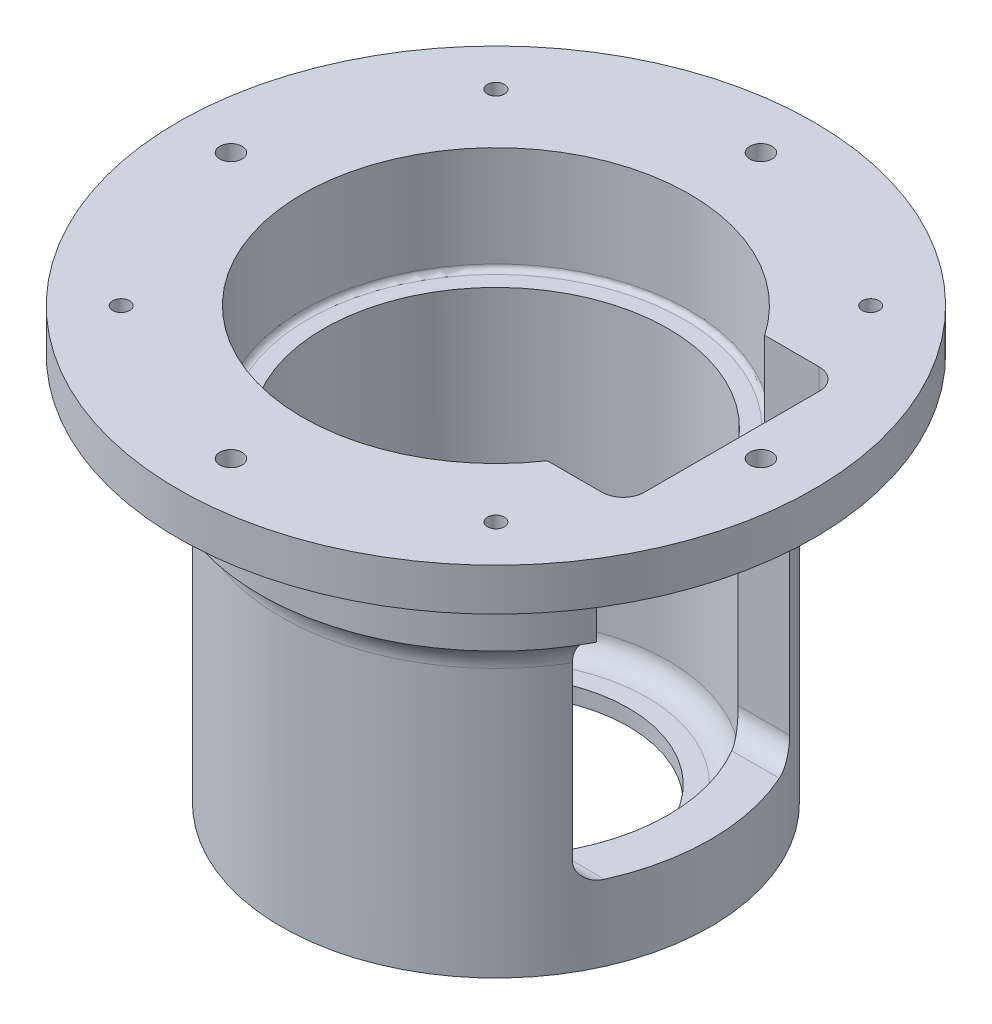
SolidWorks part; units mm, degrees
ref_plane "Front Plane" through (0, 0, 0) normal (0, 0, 1) x (1, 0, 0)
ref_plane "Top Plane" through (0, 0, 0) normal (0, 1, 0) x (1, 0, 0)
ref_plane "Right Plane" through (0, 0, 0) normal (1, 0, 0) x (0, 0, -1)
sketch "Sketch3" plane through (0, 0, 0) normal (0, 0, 1) x (1, 0, 0)
  line L0 (32.5, 12) -> (27.5, 3) construction
  line L1 (0, 0) -> (40.5, 0)
  line L2 (0, 0) -> (0, 3)
  line L3 (0, 3) -> (40.5, 3)
  line L4 (40.5, 0) -> (40.5, 3)
  line L5 (40.5, 3) -> (32.5, 3)
  line L6 (40.5, 3) -> (40.5, 81.25)
  line L7 (40.5, 81.25) -> (32.5, 81.25)
  line L8 (32.5, 3) -> (32.5, 81.25)
  line L10 (40.5, 81.25) -> (60, 81.25)
  line L11 (40.5, 81.25) -> (40.5, 73.25)
  line L12 (40.5, 73.25) -> (60, 73.25)
  line L13 (60, 81.25) -> (60, 73.25)
  line L14 (32.5, 81.25) -> (44.5, 81.25)
  line L15 (32.5, 81.25) -> (32.5, 56.25)
  line L16 (32.5, 56.25) -> (44.5, 56.25)
  line L17 (44.5, 81.25) -> (44.5, 56.25)
  line L18 (32.5, 81.25) -> (36.5, 81.25)
  line L19 (32.5, 81.25) -> (32.5, 61.25)
  line L20 (32.5, 61.25) -> (36.5, 61.25)
  line L21 (36.5, 81.25) -> (36.5, 61.25)
  dimension "D1" = 3
  dimension "D2" = 8
  dimension "D3" = 32.5
  dimension "D4" = 78.25
  dimension "D5" = 9
  dimension "D6" = 27.5
  dimension "D7" = 8
  dimension "D8" = 60
  dimension "D9" = 25
  dimension "D10" = 5
  dimension "D11" = 8
  dimension "D12" = 4
revolve "Revolve1" add sketch "Sketch3" angle 360 about L2 region at (20.25, 1.5, 0) region at (36.5, 29.625, 0) region at (37.8333, 67.0833, 0) region at (42.5, 64.75, 0) region at (42.5, 77.25, 0) region at (52.25, 77.25, 0)
sketch "Sketch5" plane through (0, 0, 0) normal (0, -1, 0) x (1, 0, 0)
  circle A0 centre (0, 0) radius 25
  dimension "D1" = 50
extrude "Cut-Extrude2" cut sketch "Sketch5" against normal through all
sketch "Sketch4" plane through (0, 81.25, 0) normal (0, 1, 0) x (1, 0, 0)
  line L1 (0, -20.5) -> (44.5, -20.5)
  line L2 (0, -20.5) -> (0, 20.5)
  line L3 (0, 20.5) -> (44.5, 20.5)
  line L4 (44.5, -20.5) -> (44.5, 20.5)
  circle A1 centre (0, 0) radius 44.5 construction
  circle A2 centre (0, 0) radius 44.5 construction
  point P4 (0, 0)
  dimension "D1" = 41
extrude "Cut-Extrude1" cut sketch "Sketch4" against normal blind 67
sketch "Sketch6" plane through (0, 81.25, 0) normal (0, 1, 0) x (1, 0, 0)
  line L0 (0, 0) -> (35.3553, 35.3553) construction
  line L1 (35.3553, 35.3553) -> (35.3553, 0) construction
  line L2 (35.3553, 0) -> (0, 0) construction
  line L3 (-35.3553, 35.3553) -> (35.3553, 35.3553) construction
  circle A0 centre (0, 0) radius 50 construction
  circle A1 centre (35.3553, 35.3553) radius 1.6
  circle A2 centre (50, 0) radius 2.1
  circle A3 centre (35.3553, -35.3553) radius 1.6
  circle A4 centre (-35.3553, -35.3553) radius 1.6
  circle A5 centre (-35.3553, 35.3553) radius 1.6
  circle A6 centre (0, 50) radius 2.1
  circle A7 centre (0, -50) radius 2.1
  circle A8 centre (-50, 0) radius 2.1
  point P5 (0, 0)
  point P9 (96.7603, 11.8849)
  point P10 (0, 0)
  point P18 (0, 0)
  point P24 (0, 0)
  dimension "D1" = 100
  dimension "D2" = 3.2
  dimension "D4" = 4.2
  dimension "D3" = 4
  dimension "D5" = 4
extrude "Cut-Extrude3" cut sketch "Sketch6" against normal through all
fillet "Fillet2" radius 4 1 edges at (0, 3, -32.5)
fillet "Fillet4" radius 4 4 edges at (30.0738, 14.25, -20.5) (30.0738, 14.25, 20.5) (44.5, 77.25, -20.5) (44.5, 77.25, 20.5)
fillet "Fillet7" radius 6 1 edges at (-40.5, 56.25, 0)
fillet "Fillet8" radius 3 1 edges at (-44.5, 73.25, 0)
fillet "Fillet9" radius 1 1 edges at (-36.5, 61.25, 0)
